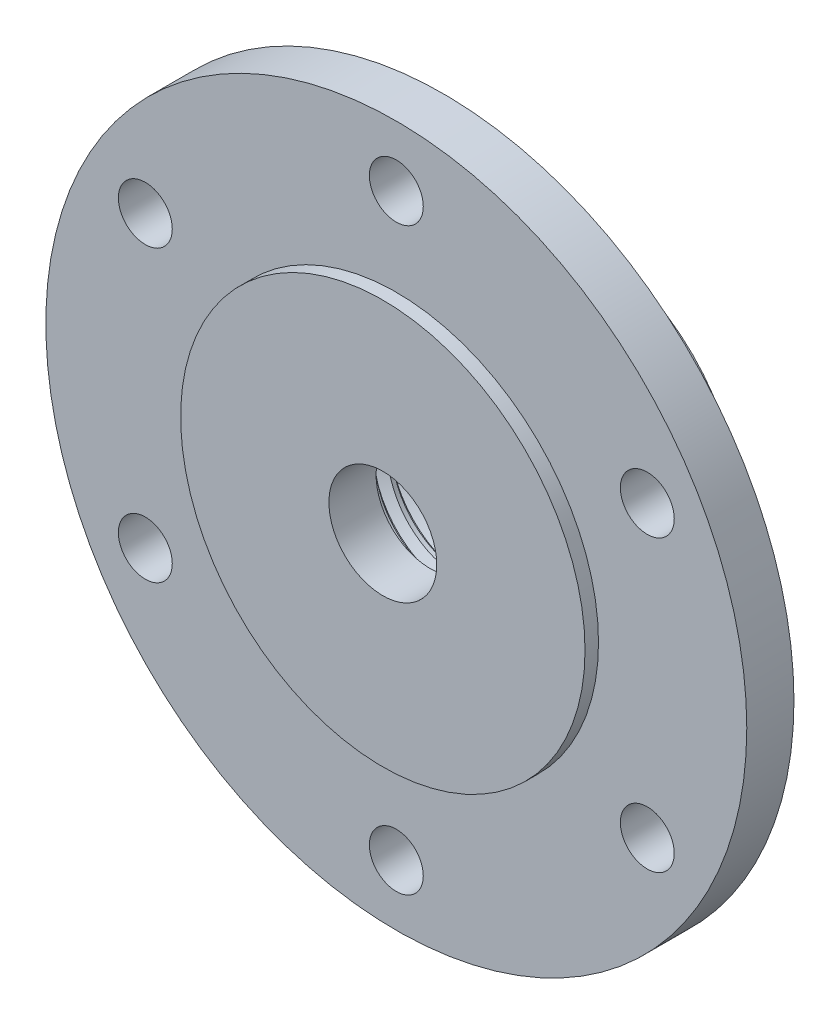
SolidWorks part; units mm, degrees
ref_plane "Front Plane" through (0, 0, 0) normal (0, 0, 1) x (1, 0, 0)
ref_plane "Top Plane" through (0, 0, 0) normal (0, 1, 0) x (1, 0, 0)
ref_plane "Right Plane" through (0, 0, 0) normal (1, 0, 0) x (0, 0, -1)
sketch "Sketch1" plane through (0, 0, 0) normal (0, 0, 1) x (1, 0, 0)
  circle A0 centre (0, 0) radius 26
  circle A1 centre (0, 0) radius 21.5 construction
  circle A2 centre (0, 21.5) radius 2
  circle A3 centre (18.6195, 10.75) radius 2
  circle A4 centre (18.6195, -10.75) radius 2
  circle A5 centre (0, -21.5) radius 2
  circle A6 centre (-18.6195, -10.75) radius 2
  circle A7 centre (-18.6195, 10.75) radius 2
  point P18 (0, 0)
  dimension "D1" = 52
  dimension "D2" = 43
  dimension "D3" = 4
  dimension "D4" = 6
extrude "Boss-Extrude1" add sketch "Sketch1" along normal blind 3.5
sketch "Sketch2" plane through (0, 0, 3.5) normal (0, 0, 1) x (1, 0, 0)
  circle A0 centre (0, 0) radius 15
  dimension "D1" = 30
extrude "Boss-Extrude2" add sketch "Sketch2" along normal blind 1
sketch "Sketch3" plane through (0, 0, 0) normal (0, 0, -1) x (-1, 0, 0)
  circle A0 centre (0, 0) radius 12
  dimension "D1" = 24
extrude "Boss-Extrude3" add sketch "Sketch3" along normal blind 10
sketch "Sketch4" plane through (0, 0, -10) normal (0, 0, -1) x (-1, 0, 0)
  circle A0 centre (0, 0) radius 6
  dimension "D1" = 12
extrude "Cut-Extrude1" cut sketch "Sketch4" against normal blind 11
sketch "Sketch5" plane through (0, 0, 4.5) normal (0, 0, 1) x (1, 0, 0)
  circle A0 centre (0, 0) radius 4
  dimension "D1" = 8
extrude "Cut-Extrude2" cut sketch "Sketch5" against normal through all
thread "Thread1" pitch 1.25 method extrude profile "Thread Profile1" start angle 0, offset 0, length 11, pitch 1.25, diameter 12
ref_plane "Plane1" through (6, 0, -10) normal (0, -1, 0) x (1, 0, 0)
sketch "Thread Profile1" plane through (6, 0, -10) normal (0, -1, 0) x (1, 0, 0)
  line L0 (0, 0) -> (0, 1.25) construction
  line L11 (0, 0) -> (0, 1.0937)
  line L12 (0, 1.0937) -> (-0.6766, 0.7031)
  line L13 (-0.6766, 0.7031) -> (-0.6766, 0.3906)
  line L15 (-0.6766, 0.3906) -> (0, 0)
  line L17 (-0.6766, 0.5469) -> (0, 0.5469) construction
  point P2 (0, 0)
  dimension "Pitch" = 1.25
  dimension "Profile_Angle" = 60
  dimension "Profile_Land" = 0.3125
  dimension "Profile_Height" = 0.6766
